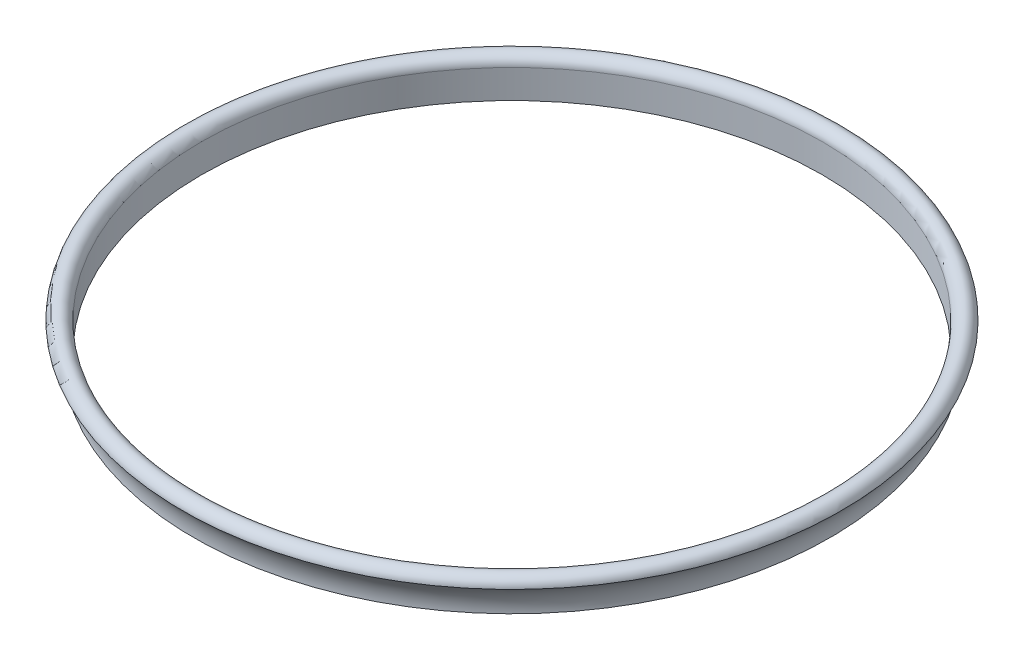
SolidWorks part; units mm, degrees
ref_plane "Front Plane" through (0, 0, 0) normal (0, 0, 1) x (1, 0, 0)
ref_plane "Top Plane" through (0, 0, 0) normal (0, 1, 0) x (1, 0, 0)
ref_plane "Right Plane" through (0, 0, 0) normal (1, 0, 0) x (0, 0, -1)
sketch "Sketch1" plane through (0, 0, 0) normal (0, 0, 1) x (1, 0, 0)
  line L7 (82.55, 0) -> (82.55, 7.62)
  line L8 (84.582, 0) -> (82.55, 0)
  line L9 (0, 0) -> (0, 14.8903) construction
  arc A0 (82.55, 7.62) -> (87.6262, 7.7583) centre (85.09, 7.62) cw
  arc A3 (87.6262, 7.7583) -> (84.582, 0) centre (94.5664, 0.5587) ccw
  dimension "D1" = 2.032
  dimension "D3" = 2.54
  dimension "D4" = 10
  dimension "D2" = 7.62
  dimension "D5" = 82.55
revolve "Revolve1" add sketch "Sketch1" angle 360 about L9
